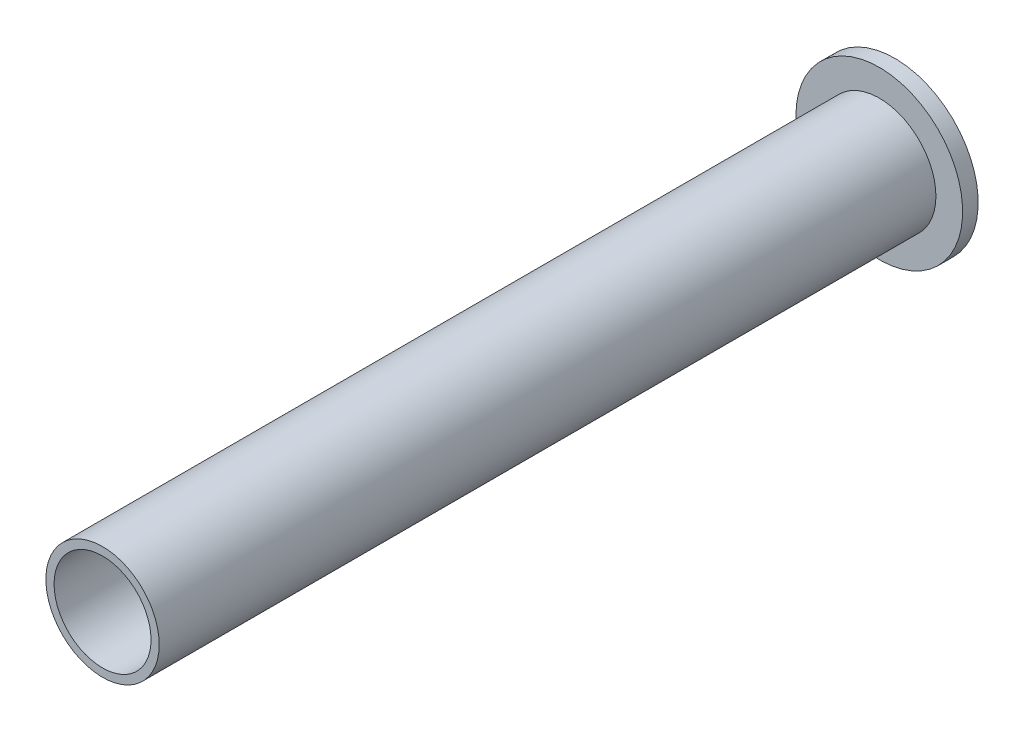
SolidWorks part; units mm, degrees
ref_plane "Front Plane" through (0, 0, 0) normal (0, 0, 1) x (1, 0, 0)
ref_plane "Top Plane" through (0, 0, 0) normal (0, 1, 0) x (1, 0, 0)
ref_plane "Right Plane" through (0, 0, 0) normal (1, 0, 0) x (0, 0, -1)
sketch "Sketch1" plane through (0, 0, 0) normal (0, 0, 1) x (1, 0, 0)
  circle A0 centre (0, 0) radius 15.6031
  circle A1 centre (0, 0) radius 18.2312
extrude "Boss-Extrude1" add sketch "Sketch1" along normal blind 250
sketch "Sketch2" plane through (0, 0, 0) normal (0, 0, -1) x (-1, 0, 0)
  circle A0 centre (0, 0) radius 15.6031
  circle A1 centre (0, 0) radius 26.8265
extrude "Boss-Extrude2" add sketch "Sketch2" along normal blind 5
